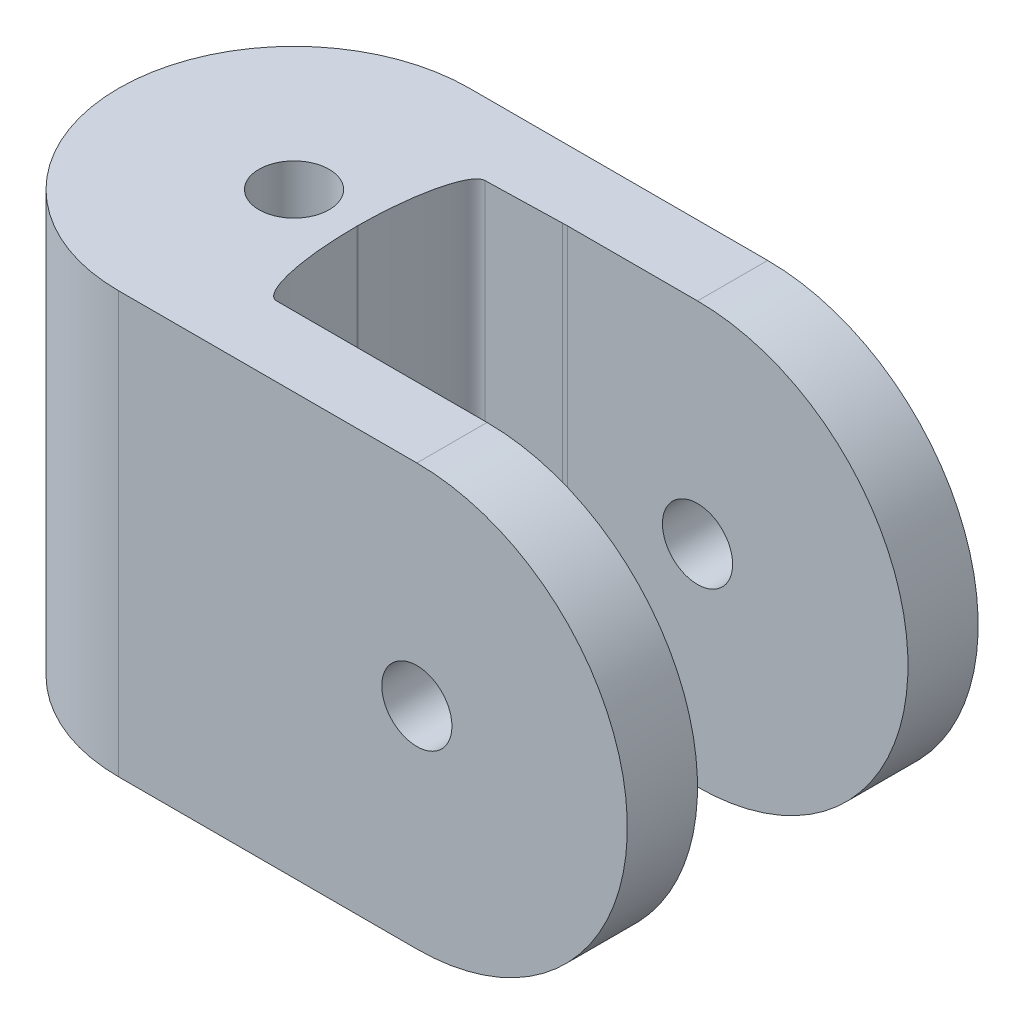
SolidWorks part; units mm, degrees
ref_plane "Front Plane" through (0, 0, 0) normal (0, 0, 1) x (1, 0, 0)
ref_plane "Top Plane" through (0, 0, 0) normal (0, 1, 0) x (1, 0, 0)
ref_plane "Right Plane" through (0, 0, 0) normal (1, 0, 0) x (0, 0, -1)
sketch "Sketch1" plane through (0, 0, 0) normal (0, 1, 0) x (1, 0, 0)
  circle A0 centre (0, 0) radius 125
  circle A1 centre (0, 0) radius 25
  dimension "D1" = 250
extrude "Boss-Extrude1" add sketch "Sketch1" along normal blind 300
ref_plane "Plane1" through (0, 0, 0) normal (0, 0, 1) x (1, 0, 0)
sketch "Sketch2" plane through (0, 0, 0) normal (0, 0, 1) x (1, 0, 0)
  line L0 (0, 300) -> (0, 0) construction
  line L1 (125, 300) -> (-125, 300) construction
  line L2 (0, 300) -> (425, 300) construction
  line L3 (425, 300) -> (425, 0) construction
  line L4 (425, 0) -> (0, 0) construction
  line L5 (0, 150) -> (425, 150) construction
  line L6 (0, 300) -> (0, 0)
  line L7 (0, 300) -> (212.5, 300)
  line L8 (0, 0) -> (212.5, 0)
  circle A0 centre (212.5, 150) radius 25
  arc A1 (212.5, 0) -> (212.5, 300) centre (212.5, 150) ccw
  dimension "D1" = 425
extrude "Boss-Extrude2" add sketch "Sketch2" along normal mid plane 250
sketch "Sketch4" plane through (0, 0, 0) normal (0, 0, 1) x (1, 0, 0)
  line L0 (0, 300) -> (0, 0)
  line L1 (0, 0) -> (212.5, 0)
  line L2 (0, 300) -> (212.5, 300)
  line L3 (3.7723, 300) -> (3.7723, 0)
  line L4 (3.7723, 0) -> (150, 0)
  line L5 (3.7723, 300) -> (150, 300)
  arc A0 (212.5, 0) -> (212.5, 300) centre (212.5, 150) ccw construction
  arc A1 (212.5, 0) -> (212.5, 300) centre (212.5, 150) ccw
  arc A2 (150, 0) -> (150, 300) centre (212.5, 150) ccw
  point P17 (0, 0)
  point P18 (154.1441, 150)
  point P19 (0, 0)
extrude "Cut-Extrude2" cut sketch "Sketch4" against normal mid plane 150 contours L4 A2 A1 L2 L3 region at (168.7573, 150, 0)
ref_plane "Plane2" through (0, 0, 0) normal (0, 1, 0) x (1, 0, 0)
sketch "Sketch5" plane through (0, 0, 0) normal (0, 1, 0) x (1, 0, 0)
  line L0 (-165, 0) -> (165, 0) construction
  line L1 (3.7723, 75) -> (3.7723, -75)
  line L2 (3.7723, -75) -> (120, -75)
  line L3 (3.7723, 75) -> (120, 75)
  circle A0 centre (0, 0) radius 25
  arc A1 (120, 75) -> (120, -75) centre (120, 0) ccw
  dimension "D1" = 120
extrude "Boss-Extrude3" add sketch "Sketch5" along normal through all contours A1 L3 L1 A0 L2 region at (37.1362, 0, 0)
sketch "Sketch6" plane through (0, 300, 0) normal (0, 1, 0) x (1, 0, 0)
  circle A0 centre (0, 0) radius 25
extrude "Cut-Extrude3" cut sketch "Sketch6" against normal through all
sketch "Sketch9" plane through (0, 0, 0) normal (0, 1, 0) x (1, 0, 0)
  line L0 (120, 75) -> (362.5, 75) construction
  line L1 (212.5, 100) -> (120, 100) construction
  line L2 (212.5, 75) -> (212.5, 125) construction
  dimension "D1" = 242.5
sketch "Sketch10" plane through (0, 0, 0) normal (0, 1, 0) x (1, 0, 0)
  line L0 (62.5, 73.5623) -> (62.5, -75) construction
  line L1 (62.5, -0.7188) -> (62.5, 73.5623) construction
  line L2 (212.5, 75) -> (212.5, -75) construction
  line L3 (62.5, 73.5623) -> (120, 75)
  line L4 (120, 75) -> (120, -75)
  line L5 (120, -75) -> (62.5, -75)
  ellipse E0 centre (62.5, -0.7188) end of major axis (62.5, 73.5623) minor radius 17.5 (62.5, 73.5623) -> (62.5, -75) ccw
  point P12 (212.5, 0)
extrude "Cut-Extrude4" cut sketch "Sketch10" along normal through all both and the other way through all contours L3 E0 L5 L4 region at (84.3346, 0, 0.428)
sketch "Sketch11" plane through (0, 0, 0) normal (0, 0, 1) x (1, 0, 0)
  circle A0 centre (212.5, 150) radius 150 construction
